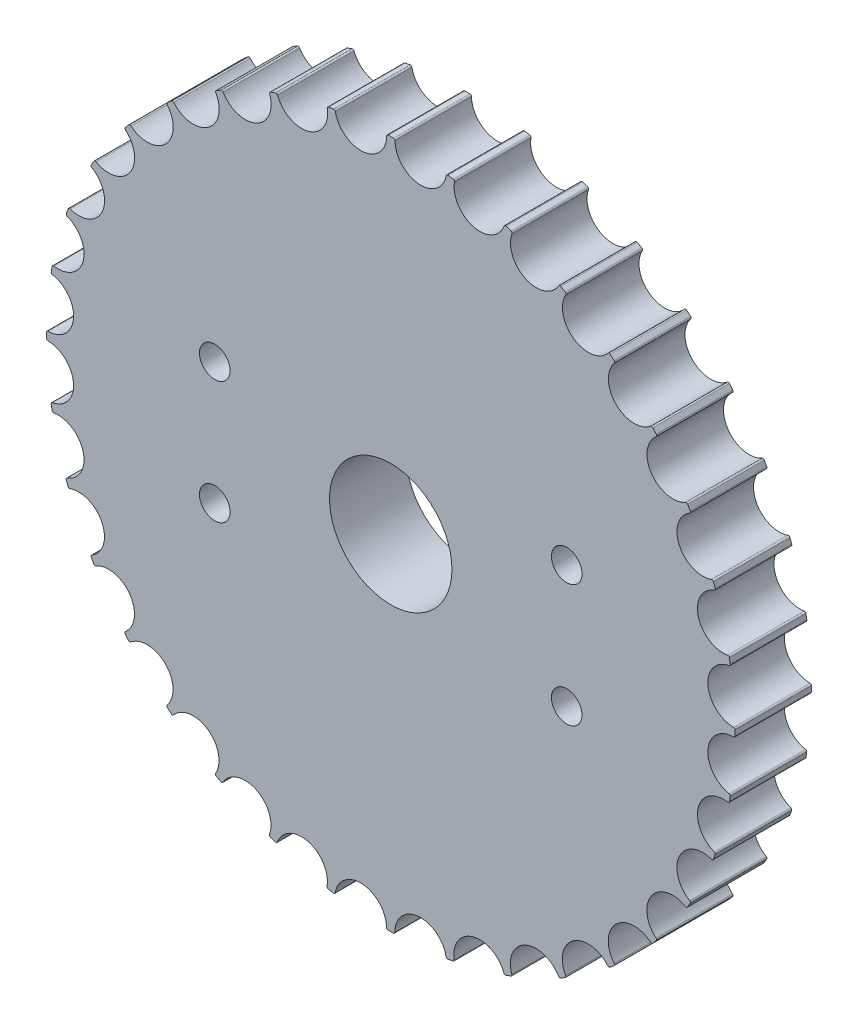
SolidWorks part; units mm, degrees
ref_plane "정면" through (0, 0, 0) normal (0, 0, 1) x (1, 0, 0)
ref_plane "윗면" through (0, 0, 0) normal (0, 1, 0) x (1, 0, 0)
ref_plane "우측면" through (0, 0, 0) normal (1, 0, 0) x (0, 0, -1)
sketch "스케치1" plane through (0, 0, 0) normal (0, 0, 1) x (1, 0, 0)
  circle A0 centre (0, 0) radius 45
  dimension "D1" = 90
extrude "보스-돌출1" add sketch "스케치1" along normal blind 10
sketch "스케치2" plane through (0, 0, 10) normal (0, 0, 1) x (1, 0, 0)
  line L0 (0, 0) -> (0, 53.4651) construction
  line L1 (0, 0) -> (9.1386, 52.0133) construction
  line L2 (0, 0) -> (-9.7027, 52.5525) construction
  circle A0 centre (3.9357, 44.8276) radius 3.38
  circle A2 centre (0, 0) radius 45 construction
  circle A6 centre (11.6601, 43.4631) radius 3.38
  circle A7 centre (19.0303, 40.778) radius 3.38
  circle A8 centre (25.8222, 36.854) radius 3.38
  circle A9 centre (31.8295, 31.8101) radius 3.38
  circle A10 centre (36.8697, 25.7997) radius 3.38
  circle A11 centre (40.7897, 19.0054) radius 3.38
  circle A12 centre (43.4702, 11.6336) radius 3.38
  circle A13 centre (44.83, 3.9083) radius 3.38
  circle A14 centre (44.8276, -3.9357) radius 3.38
  circle A15 centre (43.4631, -11.6601) radius 3.38
  circle A16 centre (40.778, -19.0303) radius 3.38
  circle A17 centre (36.854, -25.8222) radius 3.38
  circle A18 centre (31.8101, -31.8295) radius 3.38
  circle A19 centre (25.7997, -36.8697) radius 3.38
  circle A20 centre (19.0054, -40.7897) radius 3.38
  circle A21 centre (11.6336, -43.4702) radius 3.38
  circle A22 centre (3.9083, -44.83) radius 3.38
  circle A23 centre (-3.9357, -44.8276) radius 3.38
  circle A24 centre (-11.6601, -43.4631) radius 3.38
  circle A25 centre (-19.0303, -40.778) radius 3.38
  circle A26 centre (-25.8222, -36.854) radius 3.38
  circle A27 centre (-31.8295, -31.8101) radius 3.38
  circle A28 centre (-36.8697, -25.7997) radius 3.38
  circle A29 centre (-40.7897, -19.0054) radius 3.38
  circle A30 centre (-43.4702, -11.6336) radius 3.38
  circle A31 centre (-44.83, -3.9083) radius 3.38
  circle A32 centre (-44.8276, 3.9357) radius 3.38
  circle A33 centre (-43.4631, 11.6601) radius 3.38
  circle A34 centre (-40.778, 19.0303) radius 3.38
  circle A35 centre (-36.854, 25.8222) radius 3.38
  circle A36 centre (-31.8101, 31.8295) radius 3.38
  circle A37 centre (-25.7997, 36.8697) radius 3.38
  circle A38 centre (-19.0054, 40.7897) radius 3.38
  circle A39 centre (-11.6336, 43.4702) radius 3.38
  circle A40 centre (-3.9083, 44.83) radius 3.38
  dimension "D1" = 106.9058
  dimension "D2" = 36
extrude "컷-돌출2" cut sketch "스케치2" against normal blind 50
fillet "필렛1" radius 0.2 72 edges at (44.9965, -0.5599, 5) (44.9969, 0.5324, 5) (44.4101, 7.2621, 5) (44.2208, 8.338, 5) (42.4744, 14.8635, 5) (42.1011, 15.8901, 5) (39.2481, 22.0133, 5) (38.7022, 22.9595, 5) (34.8293, 28.4943, 5) (34.1273, 29.3313, 5) (29.3521, 34.1094, 5) (28.5156, 34.8118, 5) (22.9832, 38.6882, 5) (22.0373, 39.2346, 5) (44.4057, -7.2893, 5) (44.2157, -8.365, 5) (42.4653, -14.8895, 5) (42.0914, -15.9159, 5) (39.2346, -22.0373, 5) (38.6882, -22.9832, 5) (34.8118, -28.5156, 5) (34.1094, -29.3521, 5) (29.3313, -34.1273, 5) (28.4943, -34.8293, 5) (22.9595, -38.7022, 5) (22.0133, -39.2481, 5) (15.8901, -42.1011, 5) (14.8635, -42.4744, 5) (8.338, -44.2208, 5) (7.2621, -44.4101, 5) (0.5324, -44.9969, 5) (-0.5599, -44.9965, 5) (-7.2893, -44.4057, 5) (-8.365, -44.2157, 5) (-14.8895, -42.4653, 5) (-15.9159, -42.0914, 5) (-22.0373, -39.2346, 5) (-22.9832, -38.6882, 5) (-28.5156, -34.8118, 5) (-29.3521, -34.1094, 5) (-34.1273, -29.3313, 5) (-34.8293, -28.4943, 5) (-38.7022, -22.9595, 5) (-39.2481, -22.0133, 5) (-42.1011, -15.8901, 5) (-42.4744, -14.8635, 5) (-44.2208, -8.338, 5) (-44.4101, -7.2621, 5) (-44.9969, -0.5324, 5) (-44.9965, 0.5599, 5) (-44.4057, 7.2893, 5) (-44.2157, 8.365, 5) (-42.4653, 14.8895, 5) (-42.0914, 15.9159, 5) (-39.2346, 22.0373, 5) (-38.6882, 22.9832, 5) (-34.8118, 28.5156, 5) (-34.1094, 29.3521, 5) (-29.3313, 34.1273, 5) (-28.4943, 34.8293, 5) (-22.0133, 39.2481, 5) (-22.9595, 38.7022, 5) (-15.8901, 42.1011, 5) (-14.8635, 42.4744, 5) (-8.338, 44.2208, 5) (-7.2621, 44.4101, 5) (-0.5324, 44.9969, 5) (0.5599, 44.9965, 5) (7.2893, 44.4057, 5) (8.365, 44.2157, 5) (14.8895, 42.4653, 5) (15.9159, 42.0914, 5)
sketch "스케치4" plane through (0, 0, 10) normal (0, 0, 1) x (1, 0, 0)
  circle A0 centre (0, 0) radius 8
  dimension "D1" = 16
extrude "컷-돌출3" cut sketch "스케치4" against normal blind 10
sketch "스케치5" plane through (0, 0, 10) normal (0, 0, 1) x (1, 0, 0)
  line L0 (-52.1074, 0) -> (52.2141, 0) construction
  line L1 (-52.1074, -15) -> (52.2141, -15)
  line L2 (-52.1074, 15) -> (52.2141, 15)
  line L3 (0, 53.1222) -> (0, -55.2945) construction
  line L4 (-30, 53.1222) -> (-30, -55.2945)
  line L5 (30, 53.1222) -> (30, -55.2945)
  circle A0 centre (-23, 8) radius 2
  circle A1 centre (23, 8) radius 2
  circle A2 centre (23, -8) radius 2
  circle A3 centre (-23, -8) radius 2
  dimension "D5" = 4
  dimension "D7" = 7
  dimension "D6" = 7
  dimension "D1" = 15
  dimension "D2" = 15
  dimension "D3" = 30
  dimension "D4" = 30
extrude "컷-돌출4" cut sketch "스케치5" against normal blind 10 contours A3 | A0 | A1 | A2
